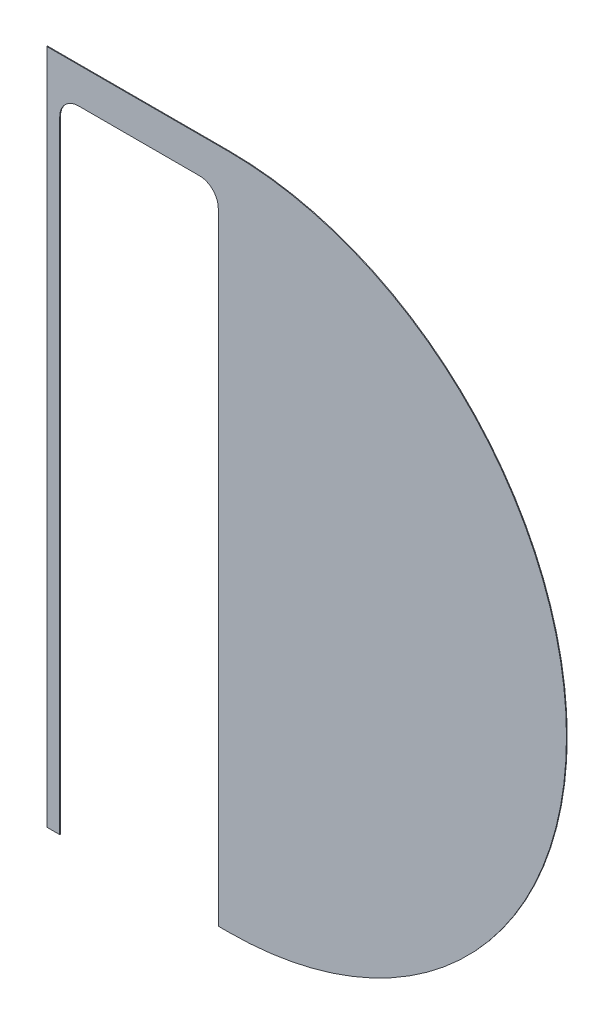
SolidWorks part; units mm, degrees
ref_plane "Front Plane" through (0, 0, 0) normal (0, 0, 1) x (1, 0, 0)
ref_plane "Top Plane" through (0, 0, 0) normal (0, 1, 0) x (1, 0, 0)
ref_plane "Right Plane" through (0, 0, 0) normal (1, 0, 0) x (0, 0, -1)
sketch "Sketch1" plane through (0, 0, 0) normal (0, 0, 1) x (1, 0, 0)
  line L1 (0, 0) -> (485, 0)
  line L2 (0, 0) -> (0, 1805)
  line L3 (0, 1805) -> (485, 1805)
  line L4 (485, 0) -> (485, 1805) construction
  arc A0 (485, 1805) -> (485, 0) centre (485, 902.5) cw
  dimension "D1" = 485
  dimension "D2" = 1805
extrude "Boss-Extrude1" add sketch "Sketch1" along normal blind 2
extrude "Cut-Extrude1" cut sketch "Sketch2" against normal through all
sketch "Sketch2" plane through (-134.8935, 114.2521, 0) normal (0, 0, -1) x (-1, 0, 0)
  line L1 (-592.7736, -114.2521) -> (-169.5721, -114.2521)
  line L2 (-592.7736, -114.2521) -> (-592.7736, 1545.5946)
  line L3 (-542.7736, 1595.5946) -> (-219.5721, 1595.5946)
  line L4 (-169.5721, -114.2521) -> (-169.5721, 1545.5946)
  arc A0 (-219.5721, 1595.5946) -> (-169.5721, 1545.5946) centre (-219.5721, 1545.5946) cw
  arc A1 (-592.7736, 1545.5946) -> (-542.7736, 1595.5946) centre (-542.7736, 1545.5946) cw
